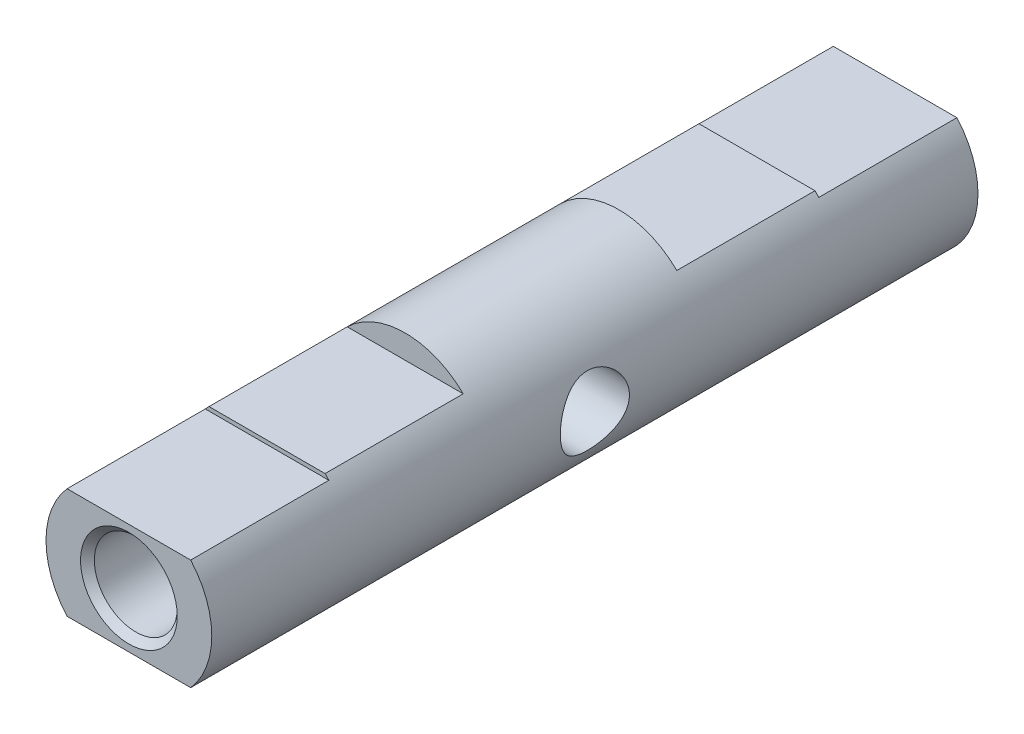
SolidWorks part; units mm, degrees
ref_plane "Front Plane" through (0, 0, 0) normal (0, 0, 1) x (1, 0, 0)
ref_plane "Top Plane" through (0, 0, 0) normal (0, 1, 0) x (1, 0, 0)
ref_plane "Right Plane" through (0, 0, 0) normal (1, 0, 0) x (0, 0, -1)
sketch "Sketch1" plane through (0, 0, 0) normal (0, 0, 1) x (1, 0, 0)
  circle A0 centre (0, 0) radius 3
  dimension "D1" = 6
extrude "Boss-Extrude1" add sketch "Sketch1" along normal blind 13.865 and the other way blind 13.865
sketch "Sketch2" plane through (0, 0, 13.865) normal (0, 0, 1) x (1, 0, 0)
  line L0 (0, 0) -> (3, 0) construction
  line L1 (-2.2361, 2) -> (2.2361, 2)
  line L2 (-2.2361, -2) -> (2.2361, -2)
  circle A0 centre (0, 0) radius 3 construction
  arc A1 (-2.2361, -2) -> (2.2361, -2) centre (0, 0) ccw
  arc A2 (2.2361, 2) -> (-2.2361, 2) centre (0, 0) ccw
  dimension "D1" = 4
extrude "Cut-Extrude1" cut sketch "Sketch2" against normal blind 5
sketch "Sketch3" plane through (0, 0, -13.865) normal (0, 0, -1) x (-1, 0, 0)
  line L0 (0, 0) -> (3, 0) construction
  line L1 (-2.2361, 2) -> (2.2361, 2)
  line L2 (-2.2361, -2) -> (2.2361, -2)
  circle A0 centre (0, 0) radius 3 construction
  arc A1 (-2.2361, -2) -> (2.2361, -2) centre (0, 0) ccw
  arc A2 (2.2361, 2) -> (-2.2361, 2) centre (0, 0) ccw
  dimension "D1" = 4
extrude "Cut-Extrude2" cut sketch "Sketch3" against normal blind 5
sketch "Sketch4" plane through (0, 0, -8.865) normal (0, 0, -1) x (-1, 0, 0)
  line L0 (-2.1, 2.1424) -> (2.1, 2.1424)
  arc A0 (2.2361, 2) -> (-2.2361, 2) centre (0, 0) ccw construction
  arc A3 (2.1, 2.1424) -> (-2.1, 2.1424) centre (0, 0) ccw
  dimension "D1" = 4.2
extrude "Cut-Extrude5" cut sketch "Sketch4" against normal blind 5
sketch "Sketch5" plane through (0, 0, 8.865) normal (0, 0, 1) x (1, 0, 0)
  line L0 (-2.1, 2.1424) -> (2.1, 2.1424)
  arc A0 (2.2361, 2) -> (-2.2361, 2) centre (0, 0) ccw construction
  arc A1 (2.1, 2.1424) -> (-2.1, 2.1424) centre (0, 0) ccw
  dimension "D1" = 4.2
extrude "Cut-Extrude6" cut sketch "Sketch5" against normal blind 5
sketch "Sketch6" plane through (0, 0, 13.865) normal (0, 0, 1) x (1, 0, 0)
  point P0 (0, 0)
sketch "Sketch7" plane through (0, 0, -13.865) normal (0, 0, -1) x (-1, 0, 0)
  point P0 (0, 0)
hole_wizard "CSK for M3 Countersunk Flat Head Screw1" positions "Sketch7" profile "Sketch8" countersink size "M3" standard "ISO"
sketch "Sketch8" plane through (0, 0, -13.865) normal (1, 0, 0) x (0, 1, 0)
  line L0 (0, 0) -> (0, 10)
  line L1 (0, 10) -> (1.5, 9.0987)
  line L2 (1.5, 9.0987) -> (1.5, 0.25)
  line L3 (1.5, 0.25) -> (1.75, 0)
  line L5 (1.75, 0) -> (0, 0)
  line L6 (-1.5, 0.25) -> (-1.75, 0) construction
  line L10 (0, 10) -> (-1.5, 9.0987) construction
  line L11 (0, -6.35) -> (0, 107.95) construction
  dimension "Hole Dia." = 3
  dimension "Hole Depth" = 10
  dimension "Near C'Sink Dia." = 3.5
  dimension "Near C'Sink Angle" = 90
  dimension "Drill Angle" = 118
hole_wizard "CSK for M3 Countersunk Flat Head Screw2" positions "Sketch9" profile "Sketch10" countersink size "M3" standard "ISO"
sketch "Sketch9" plane through (0, 0, 13.865) normal (0, 0, 1) x (1, 0, 0)
  point P0 (0, 0)
sketch "Sketch10" plane through (0, 0, 13.865) normal (1, 0, 0) x (0, -1, 0)
  line L0 (0, 0) -> (0, 10)
  line L1 (0, 10) -> (1.5, 9.0987)
  line L2 (1.5, 9.0987) -> (1.5, 0.25)
  line L3 (1.5, 0.25) -> (1.75, 0)
  line L5 (1.75, 0) -> (0, 0)
  line L6 (-1.5, 0.25) -> (-1.75, 0) construction
  line L10 (0, 10) -> (-1.5, 9.0987) construction
  line L11 (0, -6.35) -> (0, 107.95) construction
  dimension "Hole Dia." = 3
  dimension "Hole Depth" = 10
  dimension "Near C'Sink Dia." = 3.5
  dimension "Near C'Sink Angle" = 90
  dimension "Drill Angle" = 118
ref_plane "Plane1" through (5.34, 0, 0) normal (1, 0, 0) x (0, 0, -1)
sketch "Sketch11" plane through (5.34, 0, 0) normal (1, 0, 0) x (0, 0, -1)
  line L4 (-3.7, 2) -> (3.7, 2)
  line L9 (-3.7, -2) -> (3.7, -2)
  line L10 (0, 0) -> (0, 3.9248) construction
  line L11 (-3.7, 2) -> (-3.7, -2)
  line L14 (3.7, 2) -> (3.7, -2)
  dimension "D1" = 7.4
  dimension "D2" = 4
ref_plane "Plane2" through (-5.34, 0, 0) normal (1, 0, 0) x (0, 0, -1)
sketch "Sketch14" plane through (-5.34, 0, 0) normal (1, 0, 0) x (0, 0, -1)
  line L1 (3.7, -2) -> (-3.7, -2)
  line L2 (3.7, -2) -> (3.7, 2)
  line L3 (3.7, 2) -> (-3.7, 2)
  line L4 (-3.7, -2) -> (-3.7, 2)
  line L5 (3.7, -2) -> (-3.7, 2) construction
  line L6 (3.7, 2) -> (-3.7, -2) construction
  point P0 (0, 0)
  dimension "D1" = 7.4
  dimension "D2" = 4
extrude "Cut-Extrude9" cut sketch "Sketch14" along normal blind 3
sketch "Sketch15" plane through (-2.34, 0, 0) normal (-1, 0, 0) x (0, 0, 1)
  circle A0 centre (0, 0) radius 1.25
  dimension "D1" = 2.5
extrude "Cut-Extrude10" cut sketch "Sketch15" against normal through all
